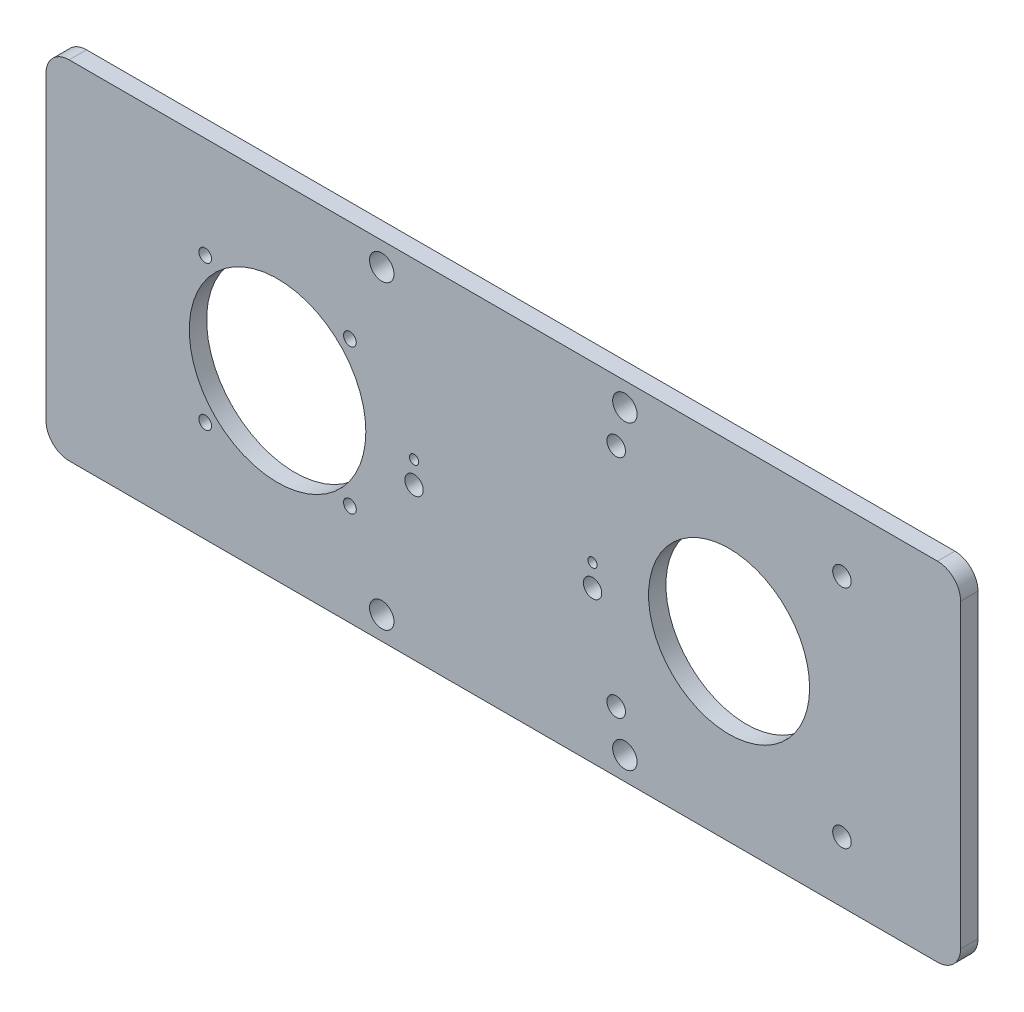
SolidWorks part; units mm, degrees
material "Dragon Plate Carbon Fiber"
ref_plane "Front" through (0, 0, 0) normal (0, 0, 1) x (1, 0, 0)
ref_plane "Top" through (0, 0, 0) normal (0, 1, 0) x (1, 0, 0)
ref_plane "Right" through (0, 0, 0) normal (1, 0, 0) x (0, 0, -1)
sketch "Sketch3" plane through (0, 0, 0) normal (0, 0, 1) x (1, 0, 0)
  line L0 (-69, 0) -> (69, 0) construction
  line L1 (-79, -10) -> (79, -10)
  line L3 (-79, -70) -> (79, -70) construction
  line L5 (-69, 0) -> (-39, 0) construction
  line L6 (-39, 0) -> (39, 0) construction
  line L7 (-39, 0) -> (-39, -40) construction
  line L8 (-39, -40) -> (39, -40) construction
  line L9 (39, -40) -> (39, 0) construction
  line L23 (-79, -10) -> (-79, -70)
  line L24 (-79, -70) -> (79, -70)
  line L25 (79, -70) -> (79, -10)
  line L27 (-21, -14) -> (-21, -66) construction
  line L28 (-51.5, -52.5) -> (-26.5, -52.5) construction
  line L29 (-51.5, -52.5) -> (-51.5, -27.5) construction
  line L30 (-51.5, -27.5) -> (-26.5, -27.5) construction
  line L31 (-26.5, -52.5) -> (-26.5, -27.5) construction
  line L32 (-51.5, -52.5) -> (-26.5, -27.5) construction
  line L33 (-51.5, -27.5) -> (-26.5, -52.5) construction
  line L34 (19.5, -59.5) -> (58.5, -59.5) construction
  line L35 (19.5, -59.5) -> (19.5, -20.5) construction
  line L36 (19.5, -20.5) -> (58.5, -20.5) construction
  line L37 (58.5, -59.5) -> (58.5, -20.5) construction
  line L38 (19.5, -59.5) -> (58.5, -20.5) construction
  line L39 (19.5, -20.5) -> (58.5, -59.5) construction
  line L44 (-21, -66) -> (21, -66) construction
  line L45 (21, -66) -> (21, -14) construction
  line L50 (21, -14) -> (-21, -14) construction
  line L65 (15.4159, -40) -> (15.4159, -43.81) construction
  line L67 (-15.42, -40) -> (-15.42, -43.81) construction
  circle A0 centre (-39, -40) radius 15.25
  circle A1 centre (39, -40) radius 13.91
  point P1 (-79, -40)
  dimension "D8" = 30.5
  dimension "D12" = 27.82
  dimension "D2" = 138
  dimension "D4" = 30
  dimension "D7" = 25
  dimension "D9" = 30.8359
  dimension "D5" = 60
  dimension "D13" = 158
  dimension "D14" = 158
  dimension "D15" = 158
  dimension "D3" = 30
  dimension "D6" = 3.81
  dimension "D10" = 69
  dimension "D11" = 15.42
  dimension "D16" = 39
  dimension "D17" = 79
  dimension "D18" = 10
  dimension "D19" = 4
  dimension "D20" = 4
  dimension "D21" = 58
  dimension "D22" = 58
extrude "Boss-Extrude2" add sketch "Sketch3" against normal blind 3
fillet "Fillet1" radius 4 4 edges at (-79, -70, -1.5) (79, -70, -1.5) (-79, -10, -1.5) (79, -10, -1.5)
sketch "Sketch4" plane through (0, 0, 0) normal (0, 0, 1) x (1, 0, 0)
  point P4 (-51.5, -27.5)
  point P6 (-26.5, -27.5)
  point P8 (-26.5, -52.5)
  point P10 (-51.5, -52.5)
hole_wizard "EVK4-Holes" positions "Sketch4" profile "Sketch6" hole size "Ø1.0" standard "ISO" end condition through all
sketch "Sketch6" plane through (-51.5, -27.5, 0) normal (1, 0, 0) x (0, -1, 0)
  line L0 (0, 0) -> (0, 3)
  line L1 (0, 3) -> (1.1, 3)
  line L2 (1.1, 3) -> (1.1, 0)
  line L5 (1.1, 0) -> (0, 0)
  line L11 (0, -6.35) -> (0, 107.95) construction
  dimension "Thru Hole Dia." = 2.2
  dimension "Thru Hole Depth" = 3
sketch "Sketch7" plane through (0, 0, 0) normal (0, 0, 1) x (1, 0, 0)
  point P0 (19.5, -20.5)
  point P1 (58.5, -20.5)
  point P3 (58.5, -59.5)
  point P5 (19.5, -59.5)
hole_wizard "FLIR-Holes" positions "Sketch7" profile "Sketch8" hole size "Ø1.0" standard "ISO" end condition through all
sketch "Sketch8" plane through (19.5, -20.5, 0) normal (1, 0, 0) x (0, -1, 0)
  line L0 (0, 0) -> (0, 3)
  line L1 (0, 3) -> (1.6, 3)
  line L2 (1.6, 3) -> (1.6, 0)
  line L5 (1.6, 0) -> (0, 0)
  line L11 (0, -6.35) -> (0, 107.95) construction
  dimension "Thru Hole Dia." = 3.2
  dimension "Thru Hole Depth" = 3
sketch "Sketch9" plane through (0, 0, 0) normal (0, 0, 1) x (1, 0, 0)
  point P0 (-15.42, -43.81)
  point P1 (15.4159, -43.81)
hole_wizard "VN-Mount-Holes" positions "Sketch9" profile "Sketch10" hole size "Ø1.0" standard "ISO" end condition through all
sketch "Sketch10" plane through (-15.42, -43.81, 0) normal (1, 0, 0) x (0, -1, 0)
  line L0 (0, 0) -> (0, 3)
  line L1 (0, 3) -> (1.5875, 3)
  line L2 (1.5875, 3) -> (1.5875, 0)
  line L5 (1.5875, 0) -> (0, 0)
  line L11 (0, -6.35) -> (0, 107.95) construction
  dimension "Thru Hole Dia." = 3.175
  dimension "Thru Hole Depth" = 3
sketch "Sketch11" plane through (0, 0, 0) normal (0, 0, 1) x (1, 0, 0)
  point P0 (-15.42, -40)
  point P1 (15.4159, -40)
hole_wizard "VN-Ref-Holes" positions "Sketch11" profile "Sketch12" hole size "Ø1.0" standard "ISO" end condition through all
sketch "Sketch12" plane through (-15.42, -40, 0) normal (1, 0, 0) x (0, -1, 0)
  line L0 (0, 0) -> (0, 3)
  line L1 (0, 3) -> (0.795, 3)
  line L2 (0.795, 3) -> (0.795, 0)
  line L5 (0.795, 0) -> (0, 0)
  line L11 (0, -6.35) -> (0, 107.95) construction
  dimension "Thru Hole Dia." = 1.59
  dimension "Thru Hole Depth" = 3
sketch "Sketch13" plane through (0, 0, 0) normal (0, 0, 1) x (1, 0, 0)
  point P0 (-21, -14)
  point P1 (21, -14)
  point P3 (21, -66)
  point P5 (-21, -66)
hole_wizard "Ø1.0mm Dowel Hole5" positions "Sketch13" profile "Sketch14" hole size "Ø1.0" standard "ISO" end condition through all
sketch "Sketch14" plane through (-21, -14, 0) normal (1, 0, 0) x (0, -1, 0)
  line L0 (0, 0) -> (0, 3)
  line L1 (0, 3) -> (2.11, 3)
  line L2 (2.11, 3) -> (2.11, 0)
  line L5 (2.11, 0) -> (0, 0)
  line L11 (0, -6.35) -> (0, 107.95) construction
  dimension "Thru Hole Dia." = 4.22
  dimension "Thru Hole Depth" = 3
equation "\"M3 Press Fit Nut Diameter\"= 4.22mm"
equation "\"M3 Clearance\"= 3.15mm"
equation "\"CF Thickness\"= 3mm"
equation "\"Tab Clearance\"= 0.1mm"
equation "\"Tab Width\"= 6mm"
equation "\"D10@Sketch3\"=138/2mm"
equation "\"D11@Sketch3\"=30.84/2"
equation "\"D1@Boss-Extrude2\"=\"CF Thickness\""
equation "\"D17@Sketch3\"=158/2mm"
